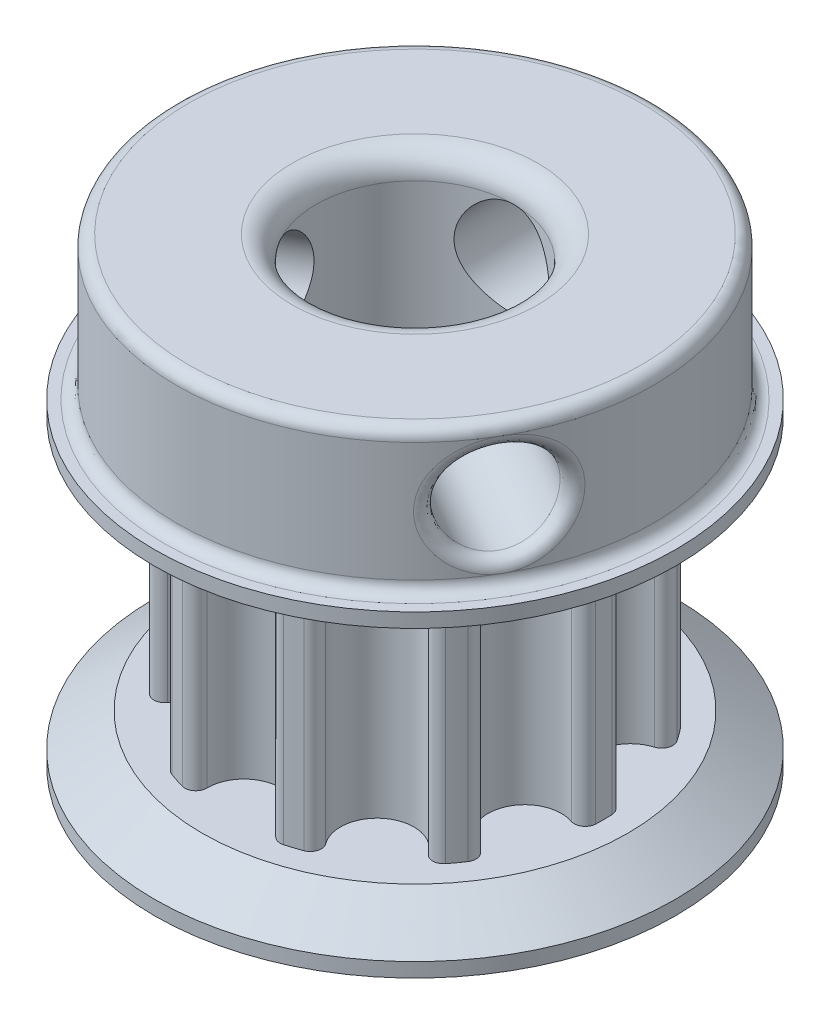
SolidWorks part; units mm, degrees
ref_plane "Plan de face" through (0, 0, 0) normal (0, 0, 1) x (1, 0, 0)
ref_plane "Plan de dessus" through (0, 0, 0) normal (0, 1, 0) x (1, 0, 0)
ref_plane "Plan de droite" through (0, 0, 0) normal (1, 0, 0) x (0, 0, -1)
sketch "Esquisse1" plane through (0, 0, 0) normal (0, 1, 0) x (1, 0, 0)
  line L0 (0, 0) -> (-2.449, 7.5372)
  line L2 (2.449, 7.5372) -> (0, 0)
  line L3 (0, 7.9251) -> (0, 0) construction
  line L4 (-2.449, 7.5372) -> (2.449, 7.5372) construction
  circle A1 centre (0, 0) radius 7.9251 construction
  arc A2 (-1.5429, 7.1881) -> (1.5429, 7.1881) centre (0, 7.1681) ccw
  arc A3 (-2.449, 7.5372) -> (-2.1236, 7.6353) centre (0, 0) cw
  arc A4 (-2.1236, 7.6353) -> (-1.5429, 7.1881) centre (-2.0008, 7.1941) cw
  arc A5 (2.449, 7.5372) -> (2.1236, 7.6353) centre (0, 0) ccw
  arc A6 (2.1236, 7.6353) -> (1.5429, 7.1881) centre (2.0008, 7.1941) ccw
  arc A7 (-1.5429, 7.1881) -> (-1.4081, 7.799) centre (0, 7.1681) cw construction
  arc A8 (1.5429, 7.1881) -> (1.4081, 7.799) centre (0, 7.1681) ccw construction
  point P0 (-1.2744, 9.7605)
  point P6 (0, 5.6251)
  point P20 (-0.8642, 8.7558)
  dimension "D2" = 1.543
  dimension "D3" = 0.458
  dimension "D1" = 4.898
  dimension "D4" = 2.3
  dimension "D5" = 36
extrude "Boss.-Extru.1" add sketch "Esquisse1" along normal blind 9.3
pattern_circular "Répétition circulaire1" count 10 over 360 about axis through (0, 9.3, 0) along (0, -1, 0) of "Boss.-Extru.1"
ref_plane "Plan1" through (0, 4.65, 0) normal (0, -1, 0) x (-1, 0, 0)
sketch "Esquisse2" plane through (0, 9.3, 0) normal (0, 1, 0) x (1, 0, 0)
  circle A0 centre (0, 0) radius 10.9251
  arc A1 (-6.2059, 4.9289) -> (-6.6054, 4.3791) centre (0, 0) ccw construction
  dimension "D1" = 3
extrude "Boss.-Extru.2" add sketch "Esquisse2" along normal blind 2
mirror "Symétrie1" about plane through (0, 4.65, 0) normal (0, -1, 0) of "Boss.-Extru.2"
chamfer "Chanfrein1" distance 2 angle 35 2 edges at (0, 9.3, 10.9251) (0, 0, 10.9251) first distance on face at (0, 9.3, 0) first distance on face at (0, 0, 0)
sketch "Esquisse4" plane through (0, 11.3, 0) normal (0, 1, 0) x (1, 0, 0)
  circle A0 centre (0, 0) radius 10
  dimension "D1" = 20
extrude "Boss.-Extru.3" add sketch "Esquisse4" along normal blind 6
sketch "Esquisse5" plane through (0, 0, 0) normal (0, 0, 1) x (1, 0, 0)
  line L0 (0, 0) -> (0, 14.3) construction
  line L1 (10, 17.3) -> (-10, 17.3) construction
  circle A0 centre (0, 14.3) radius 2
  point P3 (0, 14.6319)
  dimension "D2" = 4
  dimension "D1" = 3
extrude "Enlèv. mat.-Extru.2" cut sketch "Esquisse5" against normal through all
pattern_circular "Répétition circulaire2" count 3 over 360 about axis through (0, 17.3, 0) along (0, -1, 0) of "Enlèv. mat.-Extru.2"
sketch "Esquisse3" plane through (0, 17.3, 0) normal (0, 1, 0) x (1, 0, 0)
  circle A0 centre (0, 0) radius 4.15
  dimension "D1" = 8.3
extrude "Enlèv. mat.-Extru.1" cut sketch "Esquisse3" against normal up to next
fillet "Congé1" radius 1 2 edges at (0, -2, -4.15) (0, 17.3, 4.15)
fillet "Congé2" radius 0.5 5 edges at (0, 11.3, 10) (0, 17.3, 10) (0.4155, 12.3436, -9.9914) (-7.5148, 13.8842, 6.5976) (9.4711, 13.8842, 3.2092)
equation "\"nb_tooth\"= 10"
equation "\"D5@Esquisse1\"=360/\"nb_tooth\""
equation "\"D1@Répétition circulaire1\"=\"nb_tooth\""
